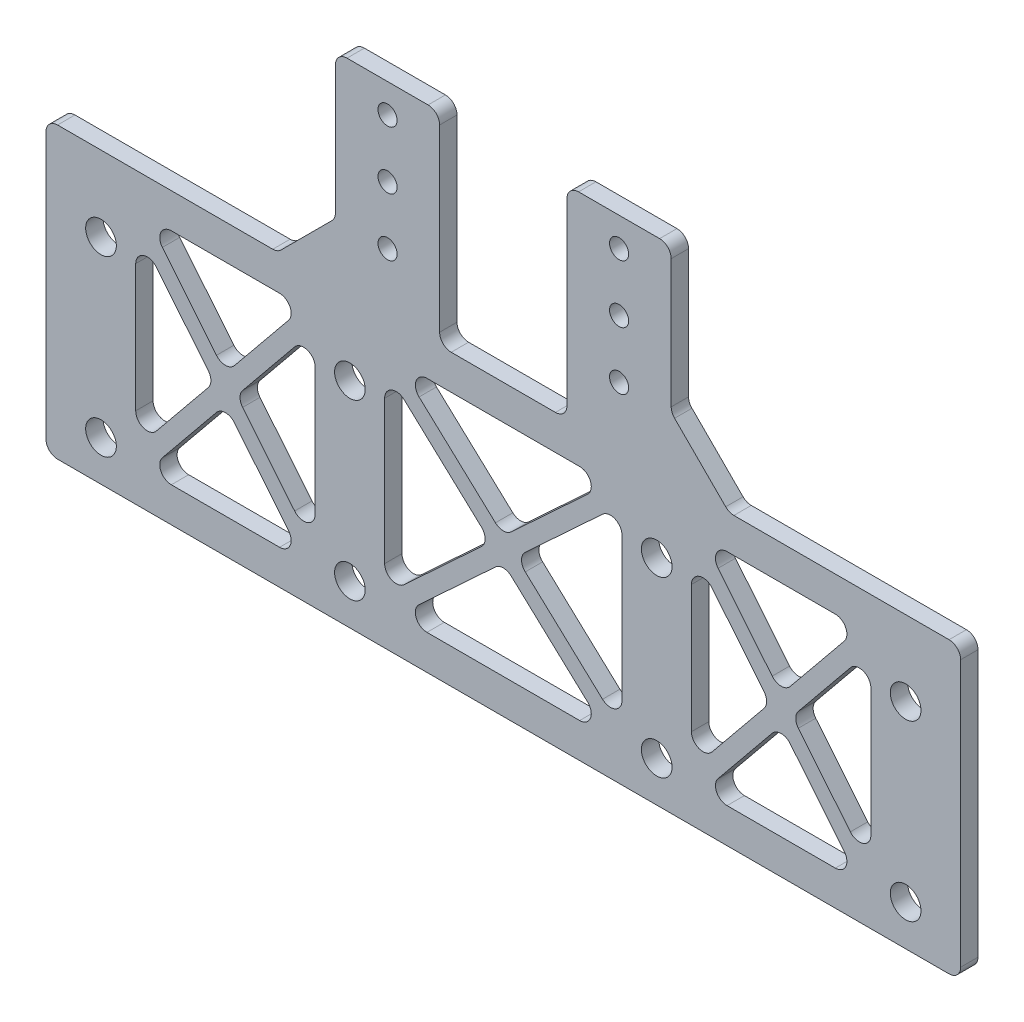
SolidWorks part; units mm, degrees
material "Thornel Mat VMA"
ref_plane "前视基准面" through (0, 0, 0) normal (0, 0, 1) x (1, 0, 0)
ref_plane "上视基准面" through (0, 0, 0) normal (0, 1, 0) x (1, 0, 0)
ref_plane "右视基准面" through (0, 0, 0) normal (1, 0, 0) x (0, 0, -1)
other "Configuration Table"
sketch "草图1" plane through (0, 0, 0) normal (0, 0, 1) x (1, 0, 0)
  line L0 (-10, 50) -> (-10, 85)
  line L1 (-10, 85) -> (10, 85)
  line L2 (-10, 50) -> (-79, 50)
  line L3 (-79, 50) -> (-79, 0)
  line L4 (0, 0) -> (0, 120.7371) construction
  line L5 (10, 50) -> (79, 50)
  line L6 (79, 50) -> (79, 0)
  line L7 (10, 50) -> (10, 85)
  line L8 (-79, 0) -> (79, 0)
  line L9 (-32.5, 6) -> (-32.5, 44)
  line L10 (63.5, 6) -> (32.5, 6)
  line L11 (63.5, 6) -> (63.5, 44)
  line L12 (63.5, 44) -> (32.5, 44)
  line L13 (32.5, 6) -> (32.5, 44)
  line L14 (63.5, 6) -> (32.5, 44) construction
  line L15 (63.5, 44) -> (32.5, 6) construction
  line L16 (20.5, 6) -> (-20.5, 6)
  line L17 (20.5, 6) -> (20.5, 44)
  line L18 (20.5, 44) -> (-20.5, 44)
  line L19 (-20.5, 6) -> (-20.5, 44)
  line L20 (20.5, 6) -> (-20.5, 44) construction
  line L21 (20.5, 44) -> (-20.5, 6) construction
  line L22 (-63.5, 6) -> (-32.5, 6)
  line L23 (-63.5, 6) -> (-63.5, 44)
  line L24 (-63.5, 44) -> (-32.5, 44)
  circle A0 centre (-6, 81) radius 1.55
  circle A1 centre (6, 81) radius 1.55
  circle A2 centre (-6, 59) radius 1.55
  circle A3 centre (6, 59) radius 1.55
  circle A4 centre (-69.5, 37) radius 2.65
  circle A5 centre (-69.5, 7) radius 2.65
  circle A6 centre (69.5, 7) radius 2.65
  circle A7 centre (69.5, 37) radius 2.65
  circle A8 centre (-26.5, 37) radius 2.65
  circle A9 centre (-26.5, 7) radius 2.65
  circle A10 centre (26.5, 7) radius 2.65
  circle A11 centre (26.5, 37) radius 2.65
  point P25 (48, 25)
  point P40 (0, 25)
  dimension "D3" = 3.1
  dimension "D4" = 4
  dimension "D5" = 22
  dimension "D6" = 4
  dimension "D8" = 30
  dimension "D10" = 5.3
  dimension "D11" = 139
  dimension "D12" = 43
  dimension "D14" = 6
  dimension "D1" = 85
  dimension "D2" = 35
  dimension "D7" = 20
  dimension "D9" = 13
  dimension "D13" = 9.5
  dimension "D15" = 6
  dimension "D16" = 6
  dimension "D17" = 6
  dimension "D18" = 6
  dimension "D19" = 6
  dimension "D20" = 6
extrude "凸台-拉伸1" add sketch "草图1" along normal blind 3
sketch "草图4" plane through (0, 0, 0) normal (0, 0, -1) x (-1, 0, 0)
  line L1 (-10, 85) -> (10, 85)
  line L2 (-10, 85) -> (-10, 50)
  line L3 (-10, 50) -> (10, 50)
  line L4 (10, 85) -> (10, 50)
  line L5 (-10, 85) -> (10, 50) construction
  line L6 (-10, 50) -> (10, 85) construction
  point P4 (0, 67.5)
extrude "切除-拉伸1" cut sketch "草图4" against normal blind 10
sketch "草图3" plane through (0, 0, 0) normal (0, 0, -1) x (-1, 0, 0)
  line L0 (0, 0) -> (0, 107.6848) construction
  line L1 (-79, 50) -> (79, 50) construction
  line L2 (-29, 85) -> (-11, 85)
  line L3 (-29, 85) -> (-29, 50)
  line L4 (-29, 50) -> (-11, 50)
  line L5 (-11, 85) -> (-11, 50)
  line L6 (-29, 85) -> (-11, 50) construction
  line L7 (-29, 50) -> (-11, 85) construction
  line L8 (29, 50) -> (11, 50)
  line L9 (11, 85) -> (11, 50)
  line L10 (29, 85) -> (11, 85)
  line L11 (29, 85) -> (29, 50)
  line L12 (29, 50) -> (11, 85) construction
  line L13 (29, 85) -> (11, 50) construction
  point P3 (-20, 67.5)
  point P14 (20, 67.5)
  dimension "D1" = 22
  dimension "D2" = 18
  dimension "D3" = 35
extrude "凸台-拉伸2" add sketch "草图3" against normal blind 3
sketch "草图5" plane through (0, 0, 0) normal (0, 0, -1) x (-1, 0, 0)
  line L0 (-20, 85) -> (-20, 49.8355) construction
  line L1 (-11, 85) -> (-29, 85) construction
  line L2 (-11, 50) -> (-11, 85) construction
  line L3 (-20, 80) -> (-20, 70) construction
  line L4 (0, 0) -> (0, 108.4309) construction
  circle A0 centre (-20, 80) radius 1.65
  circle A1 centre (-20, 70) radius 1.65
  circle A2 centre (-20, 60) radius 1.65
  circle A5 centre (20, 60) radius 1.65
  circle A6 centre (20, 70) radius 1.65
  circle A7 centre (20, 80) radius 1.65
  dimension "D5" = 3.3
  dimension "D1" = 9
  dimension "D2" = 5
  dimension "D4" = 10
  dimension "D3" = 3
extrude "切除-拉伸2" cut sketch "草图5" against normal blind 5
chamfer "倒角1" distance 10 angle 45 2 edges at (-29, 50, 1.5) (29, 50, 1.5)
fillet "圆角1" radius 2 14 edges at (79, 0, 1.5) (-79, 0, 1.5) (-79, 50, 1.5) (-39, 50, 1.5) (-29, 60, 1.5) (-29, 85, 1.5) (-11, 85, 1.5) (-11, 50, 1.5) (11, 50, 1.5) (11, 85, 1.5) (29, 85, 1.5) (39, 50, 1.5) (79, 50, 1.5) (29, 60, 1.5)
sketch "草图6" plane through (0, 0, 0) normal (0, 0, -1) x (-1, 0, 0)
  line L0 (-63.5, 44) -> (-32.5, 6)
  line L1 (-32.5, 44) -> (-63.5, 6)
  line L2 (-20.5, 44) -> (20.5, 6)
  line L3 (20.5, 44) -> (-20.5, 6)
  line L4 (32.5, 44) -> (63.5, 6)
  line L5 (63.5, 44) -> (32.5, 6)
  line L6 (63.5, 6) -> (32.5, 6) construction
  line L7 (32.5, 6) -> (32.5, 44) construction
extrude "拉伸-薄壁1" add sketch "草图6" against normal blind 3 thin thin type mid plane wall 3
fillet "圆角3" radius 2 36 edges at (0, 22.9548, 1.5) (18.2934, 6, 1.5) (-18.2934, 6, 1.5) (-20.5, 41.9548, 1.5) (-2.2066, 25, 1.5) (-20.5, 8.0452, 1.5) (20.5, 8.0452, 1.5) (2.2066, 25, 1.5) (20.5, 41.9548, 1.5) (0, 27.0452, 1.5) (-18.2934, 44, 1.5) (18.2934, 44, 1.5) (48, 27.3729, 1.5) (34.4358, 44, 1.5) (61.5642, 44, 1.5) (63.5, 8.3729, 1.5) (49.9358, 25, 1.5) (32.5, 41.6271, 1.5) (46.0642, 25, 1.5) (32.5, 8.3729, 1.5) (48, 22.6271, 1.5) (61.5642, 6, 1.5) (34.4358, 6, 1.5) (-48, 27.3729, 1.5) (-61.5642, 44, 1.5) (-34.4358, 44, 1.5) (-32.5, 8.3729, 1.5) (-46.0642, 25, 1.5) (-32.5, 41.6271, 1.5) (-63.5, 41.6271, 1.5) (-49.9358, 25, 1.5) (-63.5, 8.3729, 1.5) (-48, 22.6271, 1.5) (-34.4358, 6, 1.5) (-61.5642, 6, 1.5) (63.5, 41.6271, 1.5)
